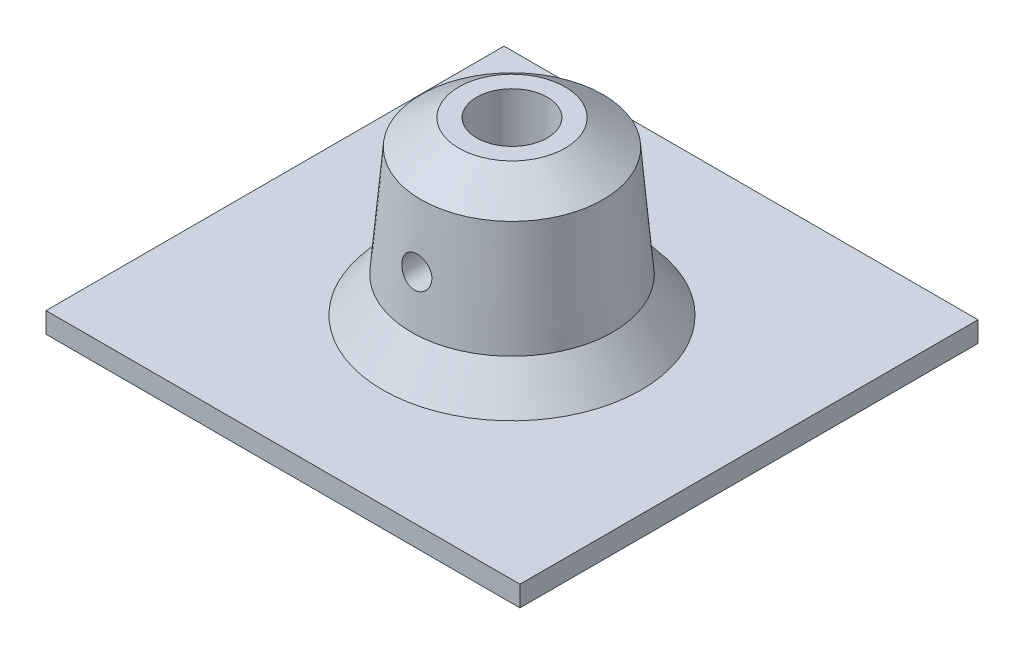
SolidWorks part; units mm, degrees
ref_plane "Front Plane" through (0, 0, 0) normal (0, 0, 1) x (1, 0, 0)
ref_plane "Top Plane" through (0, 0, 0) normal (0, 1, 0) x (1, 0, 0)
ref_plane "Right Plane" through (0, 0, 0) normal (1, 0, 0) x (0, 0, -1)
sketch "Sketch1" plane through (0, 0, 0) normal (0, 1, 0) x (1, 0, 0)
  line L1 (-13.85, 13.385) -> (13.85, 13.385)
  line L2 (-13.85, 13.385) -> (-13.85, -13.385)
  line L3 (-13.85, -13.385) -> (13.85, -13.385)
  line L4 (13.85, 13.385) -> (13.85, -13.385)
  line L5 (-13.85, 13.385) -> (13.85, -13.385) construction
  line L6 (-13.85, -13.385) -> (13.85, 13.385) construction
  point P0 (0, 0)
  dimension "D1" = 26.77
  dimension "D2" = 27.7
extrude "Boss-Extrude1" add sketch "Sketch1" along normal blind 1.2
sketch "Sketch2" plane through (0, 1.2, 0) normal (0, 1, 0) x (1, 0, 0)
  circle A0 centre (0, 0) radius 2.065 construction
  circle A1 centre (0, 0) radius 6.065
  dimension "D1" = 4.13
  dimension "D2" = 4
extrude "Boss-Extrude2" add sketch "Sketch2" along normal blind 10 draft 5
sketch "Sketch3" plane through (0, 11.2, 0) normal (0, 1, 0) x (1, 0, 0)
  circle A0 centre (0, 0) radius 2.065
  dimension "D1" = 4.13
extrude "Cut-Extrude1" cut sketch "Sketch3" against normal blind 9
chamfer "Chamfer1" distance 1.5 angle 51 2 edges at (0, 11.2, 5.1901) (0, 1.2, 6.065) first distance on face at (0, 11.2, 5.1901) first distance on face at (0, 1.2, 6.065)
sketch "Sketch4" plane through (0, 0, 0) normal (0, 0, 1) x (1, 0, 0)
  line L0 (0, 11.2) -> (0, 6.2) construction
  line L1 (3.1055, 11.2) -> (-3.1055, 11.2) construction
  circle A0 centre (0, 6.2) radius 0.875
  dimension "D2" = 1.75
  dimension "D1" = 5
extrude "Cut-Extrude2" cut sketch "Sketch4" along normal blind 9
